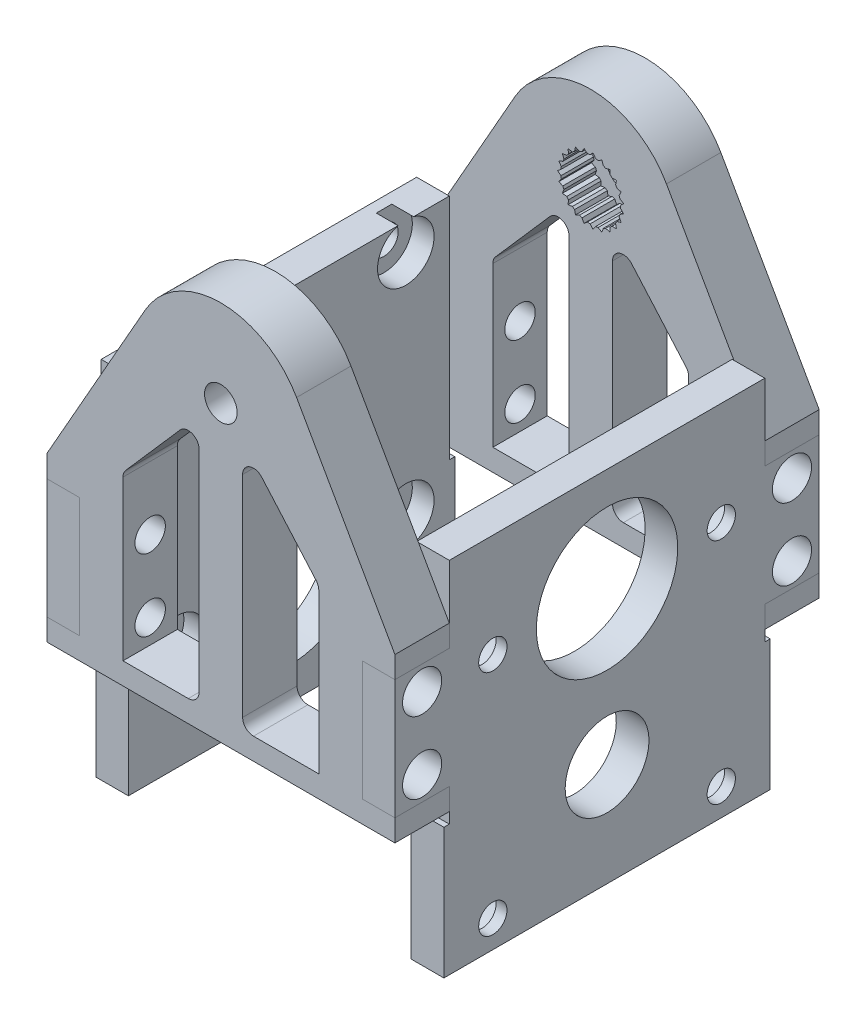
SolidWorks part; units mm, degrees
ref_plane "正面" through (0, 0, 0) normal (0, 0, 1) x (1, 0, 0)
ref_plane "平面" through (0, 0, 0) normal (0, 1, 0) x (1, 0, 0)
ref_plane "右側面" through (0, 0, 0) normal (1, 0, 0) x (0, 0, -1)
sketch "ｽｹｯﾁ1" plane through (0, 0, 0) normal (0, 0, 1) x (1, 0, 0)
  line L0 (-16, -12) -> (-16, -27)
  line L1 (-16, -27) -> (16, -27)
  line L2 (16, -27) -> (16, -12)
  line L3 (16, -12) -> (6.9593, 3.9457)
  line L4 (-6.9593, 3.9457) -> (-16, -12)
  line L5 (0, 0) -> (0, -27) construction
  line L6 (-16, -12) -> (16, -12) construction
  circle A0 centre (0, 0) radius 2.75
  arc A1 (6.9593, 3.9457) -> (-6.9593, 3.9457) centre (0, 0) ccw
  dimension "D1" = 5.5
  dimension "D6" = 8
  dimension "D2" = 16
  dimension "D3" = 16
  dimension "D4" = 12
  dimension "D5" = 15
extrude "ﾎﾞｽ - 押し出し1" add sketch "ｽｹｯﾁ1" along normal blind 3
sketch "ｽｹｯﾁ19" plane through (0, 0, 3) normal (0, 0, 1) x (1, 0, 0)
  line L0 (0, 0) -> (0, 2.75) construction
  line L1 (0, 0) -> (0.3745, 2.7244) construction
  line L2 (0, 0) -> (0.7419, 2.648) construction
  line L3 (0, 0) -> (1.0956, 2.5223) construction
  line L4 (0, 0) -> (1.4289, 2.3497) construction
  line L5 (0, 0) -> (1.7355, 2.1332) construction
  line L6 (0, 0) -> (2.0098, 1.877) construction
  line L7 (0, 0) -> (2.2467, 1.5859) construction
  line L8 (0, 0) -> (2.4417, 1.2652) construction
  line L9 (0, 0) -> (2.5912, 0.9209) construction
  line L10 (0, 0) -> (2.6925, 0.5595) construction
  line L11 (0, 0) -> (2.7436, 0.1877) construction
  line L12 (0, 0) -> (2.7436, -0.1877) construction
  line L13 (0, 0) -> (2.6925, -0.5595) construction
  line L14 (0, 0) -> (2.5912, -0.9209) construction
  line L15 (0, 0) -> (2.4417, -1.2652) construction
  line L16 (0, 0) -> (2.2467, -1.5859) construction
  line L17 (0, 0) -> (2.0098, -1.877) construction
  line L18 (0, 0) -> (1.7355, -2.1332) construction
  line L19 (0, 0) -> (1.4289, -2.3497) construction
  line L20 (0, 0) -> (1.0956, -2.5223) construction
  line L21 (0, 0) -> (0.7419, -2.648) construction
  line L22 (0, 0) -> (0.3745, -2.7244) construction
  line L23 (0, 0) -> (0, -2.75) construction
  line L24 (0, 0) -> (-0.3745, -2.7244) construction
  line L25 (0, 0) -> (-0.7419, -2.648) construction
  line L26 (0, 0) -> (-1.0956, -2.5223) construction
  line L27 (0, 0) -> (-1.4289, -2.3497) construction
  line L28 (0, 0) -> (-1.7355, -2.1332) construction
  line L29 (0, 0) -> (-2.0098, -1.877) construction
  line L30 (0, 0) -> (-2.2467, -1.5859) construction
  line L31 (0, 0) -> (-2.4417, -1.2652) construction
  line L32 (0, 0) -> (-2.5912, -0.9209) construction
  line L33 (0, 0) -> (-2.6925, -0.5595) construction
  line L34 (0, 0) -> (-2.7436, -0.1877) construction
  line L35 (0, 0) -> (-2.7436, 0.1877) construction
  line L36 (0, 0) -> (-2.6925, 0.5595) construction
  line L37 (0, 0) -> (-2.5912, 0.9209) construction
  line L38 (0, 0) -> (-2.4417, 1.2652) construction
  line L39 (0, 0) -> (-2.2467, 1.5859) construction
  line L40 (0, 0) -> (-2.0098, 1.877) construction
  line L41 (0, 0) -> (-1.7355, 2.1332) construction
  line L42 (0, 0) -> (-1.4289, 2.3497) construction
  line L43 (0, 0) -> (-1.0956, 2.5223) construction
  line L44 (0, 0) -> (-0.7419, 2.648) construction
  line L45 (0, 0) -> (-0.3745, 2.7244) construction
  line L46 (0, 0) -> (0.2081, 3.0429) construction
  line L47 (0.2081, 3.0429) -> (-0.0626, 2.7493)
  line L48 (0.2081, 3.0429) -> (0.4364, 2.7152)
  line L49 (-0.0626, 2.7493) -> (0, 0) construction
  line L50 (0, 0) -> (0.4364, 2.7152) construction
  line L51 (1.0214, 2.8739) -> (0.6815, 2.6642)
  line L52 (1.0214, 2.8739) -> (1.1527, 2.4967)
  line L53 (1.7589, 2.4918) -> (1.375, 2.3816)
  line L54 (1.7589, 2.4918) -> (1.7836, 2.0931)
  line L55 (2.3659, 1.9248) -> (1.9666, 1.9223)
  line L56 (2.3659, 1.9248) -> (2.2822, 1.5343)
  line L57 (2.7975, 1.2151) -> (2.4123, 1.3204)
  line L58 (2.7975, 1.2151) -> (2.6115, 0.8617)
  line L59 (3.0216, 0.4153) -> (2.679, 0.6206)
  line L60 (3.0216, 0.4153) -> (2.7472, 0.1252)
  line L61 (3.0216, -0.4153) -> (2.7472, -0.1252)
  line L62 (3.0216, -0.4153) -> (2.679, -0.6206)
  line L63 (2.7975, -1.2151) -> (2.6115, -0.8617)
  line L64 (2.7975, -1.2151) -> (2.4123, -1.3204)
  line L65 (2.3659, -1.9248) -> (2.2822, -1.5343)
  line L66 (2.3659, -1.9248) -> (1.9666, -1.9223)
  line L67 (1.7589, -2.4918) -> (1.7836, -2.0931)
  line L68 (1.7589, -2.4918) -> (1.375, -2.3816)
  line L69 (1.0214, -2.8739) -> (1.1527, -2.4967)
  line L70 (1.0214, -2.8739) -> (0.6815, -2.6642)
  line L71 (0.2081, -3.0429) -> (0.4364, -2.7152)
  line L72 (0.2081, -3.0429) -> (-0.0626, -2.7493)
  line L73 (-0.6205, -2.9862) -> (-0.3123, -2.7322)
  line L74 (-0.6205, -2.9862) -> (-0.802, -2.6304)
  line L75 (-1.4032, -2.708) -> (-1.0379, -2.5466)
  line L76 (-1.4032, -2.708) -> (-1.482, -2.3165)
  line L77 (-2.0818, -2.229) -> (-1.6865, -2.1722)
  line L78 (-2.0818, -2.229) -> (-2.052, -1.8308)
  line L79 (-2.606, -1.5847) -> (-2.21, -1.6366)
  line L80 (-2.606, -1.5847) -> (-2.4699, -1.2093)
  line L81 (-2.9369, -0.8229) -> (-2.5696, -0.9797)
  line L82 (-2.9369, -0.8229) -> (-2.7045, -0.4981)
  line L83 (-3.05, 0) -> (-2.7386, -0.2501)
  line L84 (-3.05, 0) -> (-2.7386, 0.2501)
  line L85 (-2.9369, 0.8229) -> (-2.7045, 0.4981)
  line L86 (-2.9369, 0.8229) -> (-2.5696, 0.9797)
  line L87 (-2.606, 1.5847) -> (-2.4699, 1.2093)
  line L88 (-2.606, 1.5847) -> (-2.21, 1.6366)
  line L89 (-2.0818, 2.229) -> (-2.052, 1.8308)
  line L90 (-2.0818, 2.229) -> (-1.6865, 2.1722)
  line L91 (-1.4032, 2.708) -> (-1.482, 2.3165)
  line L92 (-1.4032, 2.708) -> (-1.0379, 2.5466)
  line L93 (-0.6205, 2.9862) -> (-0.802, 2.6304)
  line L94 (-0.6205, 2.9862) -> (-0.3123, 2.7322)
  circle A0 centre (0, 0) radius 2.75 construction
  arc A1 (0, 2.75) -> (0.3745, 2.7244) centre (0, 0) cw construction
  circle A2 centre (0, 0) radius 3.05 construction
  arc A3 (-0.0626, 2.7493) -> (0.4364, 2.7152) centre (0, 0) cw
  arc A4 (0.6815, 2.6642) -> (1.1527, 2.4967) centre (0, 0) cw
  arc A5 (1.375, 2.3816) -> (1.7836, 2.0931) centre (0, 0) cw
  arc A6 (1.9666, 1.9223) -> (2.2822, 1.5343) centre (0, 0) cw
  arc A7 (2.4123, 1.3204) -> (2.6115, 0.8617) centre (0, 0) cw
  arc A8 (2.679, 0.6206) -> (2.7472, 0.1252) centre (0, 0) cw
  arc A9 (2.7472, -0.1252) -> (2.679, -0.6206) centre (0, 0) cw
  arc A10 (2.6115, -0.8617) -> (2.4123, -1.3204) centre (0, 0) cw
  arc A11 (2.2822, -1.5343) -> (1.9666, -1.9223) centre (0, 0) cw
  arc A12 (1.7836, -2.0931) -> (1.375, -2.3816) centre (0, 0) cw
  arc A13 (1.1527, -2.4967) -> (0.6815, -2.6642) centre (0, 0) cw
  arc A14 (0.4364, -2.7152) -> (-0.0626, -2.7493) centre (0, 0) cw
  arc A15 (-0.3123, -2.7322) -> (-0.802, -2.6304) centre (0, 0) cw
  arc A16 (-1.0379, -2.5466) -> (-1.482, -2.3165) centre (0, 0) cw
  arc A17 (-1.6865, -2.1722) -> (-2.052, -1.8308) centre (0, 0) cw
  arc A18 (-2.21, -1.6366) -> (-2.4699, -1.2093) centre (0, 0) cw
  arc A19 (-2.5696, -0.9797) -> (-2.7045, -0.4981) centre (0, 0) cw
  arc A20 (-2.7386, -0.2501) -> (-2.7386, 0.2501) centre (0, 0) cw
  arc A21 (-2.7045, 0.4981) -> (-2.5696, 0.9797) centre (0, 0) cw
  arc A22 (-2.4699, 1.2093) -> (-2.21, 1.6366) centre (0, 0) cw
  arc A23 (-2.052, 1.8308) -> (-1.6865, 2.1722) centre (0, 0) cw
  arc A24 (-1.482, 2.3165) -> (-1.0379, 2.5466) centre (0, 0) cw
  arc A25 (-0.802, 2.6304) -> (-0.3123, 2.7322) centre (0, 0) cw
  point P7 (0.1877, 2.7436)
  point P52 (0, 0)
  point P60 (0.1877, 2.7436)
  point P126 (0, 0)
  dimension "D2" = 6.1
  dimension "D3" = 10.435
  dimension "D1" = 46
  dimension "D4" = 23
extrude "ｶｯﾄ - 押し出し6" cut sketch "ｽｹｯﾁ19" against normal through all
sketch "ｽｹｯﾁ2" plane through (0, 0, 0) normal (0, 0, -1) x (-1, 0, 0)
  line L5 (16, -12) -> (6.9593, 3.9457)
  line L6 (-6.9593, 3.9457) -> (-16, -12)
  line L7 (-16, -12) -> (-16, -27)
  line L8 (-16, -27) -> (16, -27)
  line L9 (16, -27) -> (16, -12)
  line L10 (16, -12) -> (6.9593, 3.9457)
  line L11 (-6.9593, 3.9457) -> (-16, -12)
  line L12 (-16, -12) -> (-16, -27)
  line L13 (-16, -27) -> (16, -27)
  line L14 (16, -27) -> (16, -12)
  arc A1 (6.9593, 3.9457) -> (-6.9593, 3.9457) centre (0, 0) ccw
  arc A2 (6.9593, 3.9457) -> (-6.9593, 3.9457) centre (0, 0) ccw
  dimension "D1" = 0
extrude "ﾎﾞｽ - 押し出し2" add sketch "ｽｹｯﾁ2" along normal blind 2
ref_plane "平面1" through (0, 0, 33.5) normal (0, 0, 1) x (1, 0, 0)
sketch "ｽｹｯﾁ3" plane through (0, 0, 33.5) normal (0, 0, 1) x (1, 0, 0)
  line L5 (-6.9593, 3.9457) -> (-16, -12)
  line L6 (-16, -12) -> (-16, -27)
  line L7 (-16, -27) -> (16, -27)
  line L8 (16, -27) -> (16, -12)
  line L9 (16, -12) -> (6.9593, 3.9457)
  line L10 (-6.9593, 3.9457) -> (-16, -12)
  line L11 (-16, -12) -> (-16, -27)
  line L12 (-16, -27) -> (16, -27)
  line L13 (16, -27) -> (16, -12)
  line L14 (16, -12) -> (6.9593, 3.9457)
  circle A0 centre (0, 0) radius 2.75 construction
  arc A1 (6.9593, 3.9457) -> (-6.9593, 3.9457) centre (0, 0) ccw
  arc A2 (6.9593, 3.9457) -> (-6.9593, 3.9457) centre (0, 0) ccw
  circle A3 centre (0, 0) radius 2.75 construction
  circle A4 centre (0, 0) radius 3.6
  dimension "D2" = 7.2
  dimension "D1" = 0
extrude "ﾎﾞｽ - 押し出し3" add sketch "ｽｹｯﾁ3" against normal blind 1.5 separate body
sketch "ｽｹｯﾁ4" plane through (0, 0, 33.5) normal (0, 0, 1) x (1, 0, 0)
  line L5 (-6.9593, 3.9457) -> (-16, -12)
  line L6 (-16, -12) -> (-16, -27)
  line L7 (-16, -27) -> (16, -27)
  line L8 (16, -27) -> (16, -12)
  line L9 (16, -12) -> (6.9593, 3.9457)
  line L10 (-6.9593, 3.9457) -> (-16, -12)
  line L11 (-16, -12) -> (-16, -27)
  line L12 (-16, -27) -> (16, -27)
  line L13 (16, -27) -> (16, -12)
  line L14 (16, -12) -> (6.9593, 3.9457)
  arc A1 (6.9593, 3.9457) -> (-6.9593, 3.9457) centre (0, 0) ccw
  arc A2 (6.9593, 3.9457) -> (-6.9593, 3.9457) centre (0, 0) ccw
  dimension "D1" = 0
extrude "ﾎﾞｽ - 押し出し4" add sketch "ｽｹｯﾁ4" along normal blind 3.5
sketch "ｽｹｯﾁ5" plane through (0, 0, -2) normal (0, 0, -1) x (-1, 0, 0)
  line L0 (-16, -12) -> (-16, -27) construction
  line L1 (-16, -14) -> (-13, -14)
  line L2 (-16, -14) -> (-16, -25)
  line L3 (-16, -25) -> (-13, -25)
  line L4 (-13, -14) -> (-13, -25)
  line L5 (-16, -14) -> (-13, -25) construction
  line L6 (-16, -25) -> (-13, -14) construction
  line L7 (16, -27) -> (16, -12) construction
  line L8 (16, -14) -> (13, -14)
  line L9 (16, -14) -> (16, -25)
  line L10 (16, -25) -> (13, -25)
  line L11 (13, -14) -> (13, -25)
  line L12 (16, -14) -> (13, -25) construction
  line L13 (16, -25) -> (13, -14) construction
  line L14 (-16, -27) -> (16, -27) construction
  line L15 (-16, -12) -> (16, -12) construction
  line L16 (-6.9593, 3.9457) -> (-16, -12) construction
  point P4 (-14.5, -19.5)
  point P11 (14.5, -19.5)
  dimension "D1" = 3
  dimension "D2" = 3
  dimension "D3" = 2
  dimension "D4" = 2
extrude "ｶｯﾄ - 押し出し1" cut sketch "ｽｹｯﾁ5" against normal through all
sketch "ｽｹｯﾁ6" plane through (13, 0, 0) normal (1, 0, 0) x (0, 0, -1)
  line L0 (2, -14) -> (-3, -14)
  line L1 (-3, -14) -> (-3, -7)
  line L2 (-3, -7) -> (-32, -7)
  line L3 (-32, -12) -> (-32, 3.9457) construction
  line L4 (-32, -7) -> (-32, -14)
  line L5 (-32, -14) -> (-37, -14)
  line L6 (-37, -14) -> (-37, -25)
  line L7 (-37, -25) -> (-32, -25)
  line L8 (-32, -25) -> (-32, -40)
  line L9 (-32, -40) -> (-3, -40)
  line L10 (-3, -40) -> (-3, -25)
  line L11 (-3, -25) -> (2, -25)
  line L12 (2, -25) -> (2, -14)
  line L13 (-17.5, -7) -> (-17.5, -40) construction
  line L14 (0, 0) -> (-33.5, 0) construction
  line L15 (-7, -37.5) -> (-28, -37.5) construction
  line L16 (-7, -37.5) -> (-7, -16.5) construction
  line L17 (-7, -16.5) -> (-28, -16.5) construction
  line L18 (-28, -37.5) -> (-28, -16.5) construction
  line L19 (-7, -37.5) -> (-28, -16.5) construction
  line L20 (-7, -16.5) -> (-28, -37.5) construction
  line L21 (-33.5, 3.3394) -> (-33.5, -3.3394) construction
  line L22 (2, -23.5) -> (-37, -23.5) construction
  circle A0 centre (-17.5, -16.5) radius 6.5
  circle A1 centre (-28, -16.5) radius 1.3
  circle A2 centre (-7, -16.5) radius 1.3
  circle A3 centre (-28, -37.5) radius 1.3
  circle A4 centre (-7, -37.5) radius 1.3
  circle A5 centre (-17.5, -30.5) radius 6.5 construction
  circle A6 centre (-17.5, -30.5) radius 3.85
  point P24 (-17.5, -27)
  point P43 (-17.5, -23.5)
  dimension "D6" = 2.6
  dimension "D8" = 13
  dimension "D10" = 7.7
  dimension "D1" = 21
  dimension "D2" = 21
  dimension "D3" = 14.5
  dimension "D4" = 13
  dimension "D5" = 21
  dimension "D7" = 20
  dimension "D9" = 27
extrude "ﾎﾞｽ - 押し出し5" add sketch "ｽｹｯﾁ6" along normal up to surface (3 mm away) separate body up to face at (16, -13, 0.5)
sketch "ｽｹｯﾁ8" plane through (-13, 0, 0) normal (-1, 0, 0) x (0, 0, 1)
  line L0 (3, -7) -> (3, -40) construction
  line L1 (32, -7) -> (32, -40) construction
  line L2 (3, -23.5) -> (32, -23.5) construction
  line L12 (-2, -14) -> (-2, -25)
  line L13 (-2, -25) -> (3, -25)
  line L14 (3, -25) -> (3, -40)
  line L15 (3, -40) -> (32, -40)
  line L16 (32, -40) -> (32, -25)
  line L17 (32, -25) -> (37, -25)
  line L18 (37, -25) -> (37, -14)
  line L19 (37, -14) -> (32, -14)
  line L20 (32, -14) -> (32, -7)
  line L21 (32, -7) -> (3, -7)
  line L22 (3, -7) -> (3, -14)
  line L23 (3, -14) -> (-2, -14)
  line L24 (-2, -14) -> (-2, -25)
  line L25 (-2, -25) -> (3, -25)
  line L26 (3, -25) -> (3, -40)
  line L27 (3, -40) -> (32, -40)
  line L28 (32, -40) -> (32, -25)
  line L29 (32, -25) -> (37, -25)
  line L30 (37, -25) -> (37, -14)
  line L31 (37, -14) -> (32, -14)
  line L32 (32, -14) -> (32, -7)
  line L33 (32, -7) -> (3, -7)
  line L34 (3, -7) -> (3, -14)
  line L35 (3, -14) -> (-2, -14)
  circle A0 centre (28, -37.5) radius 1.3 construction
  circle A1 centre (28, -16.5) radius 1.3 construction
  circle A2 centre (7, -37.5) radius 1.3 construction
  circle A3 centre (17.5, -16.5) radius 6.5 construction
  circle A4 centre (7, -16.5) radius 1.3 construction
  circle A5 centre (28, -37.5) radius 1.3 construction
  circle A6 centre (28, -16.5) radius 1.3 construction
  circle A7 centre (7, -37.5) radius 1.3 construction
  circle A8 centre (17.5, -16.5) radius 6.5 construction
  circle A9 centre (7, -16.5) radius 1.3 construction
  circle A10 centre (28, -9.5) radius 1.3
  circle A11 centre (7, -9.5) radius 1.3
  circle A12 centre (28, -30.5) radius 1.3
  circle A13 centre (17.5, -30.5) radius 6.5
  circle A14 centre (7, -30.5) radius 1.3
  circle A15 centre (17.5, -16.5) radius 3.85
  dimension "D2" = 7.7
  dimension "D1" = 0
extrude "ﾎﾞｽ - 押し出し6" add sketch "ｽｹｯﾁ8" along normal up to surface (3 mm away) separate body up to face at (-16, -26, 0.5)
sketch "ｽｹｯﾁ7" plane through (0, 0, -2) normal (0, 0, -1) x (-1, 0, 0)
  line L0 (0, 0) -> (0, -13.5) construction
  line L1 (-16, -27) -> (16, -27) construction
  line L2 (9, -25) -> (-9, -25) construction
  line L3 (9, -25) -> (9, -2) construction
  line L4 (9, -2) -> (-9, -2) construction
  line L5 (-9, -25) -> (-9, -2) construction
  line L6 (9, -25) -> (-9, -2) construction
  line L7 (9, -2) -> (-9, -25) construction
  line L8 (-13, -25) -> (-13, -14) construction
  line L9 (-9, -25) -> (-3, -25)
  line L10 (-2, -24) -> (-2, -4.6614)
  line L11 (-3.7526, -4.0029) -> (-8.7526, -9.7172)
  line L12 (-9, -10.3757) -> (-9, -25)
  line L15 (-16, -14) -> (-13, -14) construction
  line L16 (9, -25) -> (3, -25)
  line L17 (9, -10.3757) -> (9, -25)
  line L18 (3.7526, -4.0029) -> (8.7526, -9.7172)
  line L19 (2, -24) -> (2, -4.6614)
  circle A0 centre (0, 0) radius 1.5
  arc A2 (3, -25) -> (2, -24) centre (3, -24) cw
  arc A3 (-3, -25) -> (-2, -24) centre (-3, -24) ccw
  arc A5 (-2, -4.6614) -> (-3.7526, -4.0029) centre (-3, -4.6614) ccw
  arc A6 (3.7526, -4.0029) -> (2, -4.6614) centre (3, -4.6614) ccw
  arc A7 (9, -10.3757) -> (8.7526, -9.7172) centre (8, -10.3757) ccw
  arc A8 (-8.7526, -9.7172) -> (-9, -10.3757) centre (-8, -10.3757) ccw
  point P28 (2, -25)
  point P31 (-2, -25)
  point P37 (-2, -2)
  point P40 (2, -2)
  point P43 (9, -10)
  point P46 (-9, -10)
  dimension "D1" = 3
  dimension "D8" = 1
  dimension "D2" = 2
  dimension "D3" = 4
  dimension "D4" = 23
  dimension "D5" = 4
  dimension "D6" = 7
extrude "ｶｯﾄ - 押し出し2" cut sketch "ｽｹｯﾁ7" against normal through all
sketch "ｽｹｯﾁ10" plane through (16, 0, 0) normal (1, 0, 0) x (0, 0, -1)
  line L4 (-34.5, -12) -> (-34.5, -27) construction
  line L5 (-32, -12) -> (-37, -12) construction
  line L6 (-32, -27) -> (-37, -27) construction
  line L8 (-0.5, -12) -> (-0.5, -27) construction
  line L9 (-3, -12) -> (2, -12) construction
  line L10 (-3, -27) -> (2, -27) construction
  line L11 (-37, -14) -> (-32, -14) construction
  line L14 (-32, -25) -> (-37, -25) construction
  line L15 (-3, -14) -> (2, -14) construction
  line L16 (2, -25) -> (-3, -25) construction
  point P26 (-34.5, -16.2)
  point P28 (-34.5, -22.8)
  point P30 (-0.5, -16.2)
  point P32 (-0.5, -22.8)
  dimension "D1" = 2.2
  dimension "D2" = 2.2
  dimension "D3" = 2.2
  dimension "D4" = 2.2
hole_wizard "Ø2.8 (2.8) 直径の穴1" positions "ｽｹｯﾁ10" profile "ｽｹｯﾁ11" hole size "Ø2.8" standard "JIS"
sketch "ｽｹｯﾁ11" plane through (16, -22.8, 0.5) normal (0, 1, 0) x (0, 0, -1)
  line L0 (0, 0) -> (0, 14)
  line L1 (0, 14) -> (1.4, 13.1588)
  line L2 (1.4, 13.1588) -> (1.4, 0)
  line L5 (1.4, 0) -> (0, 0)
  line L10 (0, 14) -> (-1.4, 13.1588) construction
  line L11 (0, -6.35) -> (0, 107.95) construction
  dimension "穴の直径" = 2.8
  dimension "穴の深さ" = 14
  dimension "ﾄﾞﾘﾙ角度" = 118
hole_wizard "Ø2.8 (2.8) 直径の穴2" positions "ｽｹｯﾁ12" profile "ｽｹｯﾁ13" hole size "Ø2.8" standard "JIS"
sketch "ｽｹｯﾁ12" plane through (-16, 0, 0) normal (-1, 0, 0) x (0, 0, 1)
  point P0 (34.5, -16.2)
  point P3 (34.5, -22.8)
  point P6 (0.5, -16.2)
  point P9 (0.5, -22.8)
sketch "ｽｹｯﾁ13" plane through (-16, -16.2, 34.5) normal (0, 1, 0) x (0, 0, 1)
  line L0 (0, 0) -> (0, 14)
  line L1 (0, 14) -> (1.4, 13.1588)
  line L2 (1.4, 13.1588) -> (1.4, 0)
  line L5 (1.4, 0) -> (0, 0)
  line L10 (0, 14) -> (-1.4, 13.1588) construction
  line L11 (0, -6.35) -> (0, 107.95) construction
  dimension "穴の直径" = 2.8
  dimension "穴の深さ" = 14
  dimension "ﾄﾞﾘﾙ角度" = 118
hole_wizard "Ø3.6 (3.6) 直径の穴1" positions "ｽｹｯﾁ14" profile "ｽｹｯﾁ16" hole size "Ø3.6" standard "JIS" end condition through all
sketch "ｽｹｯﾁ14" plane through (16, 0, 0) normal (1, 0, 0) x (0, 0, -1)
  point P0 (-34.5, -16.2)
  point P3 (-34.5, -22.8)
  point P6 (-0.5, -16.2)
  point P9 (-0.5, -22.8)
sketch "ｽｹｯﾁ16" plane through (16, -16.2, 34.5) normal (0, 1, 0) x (0, 0, -1)
  line L0 (0, 0) -> (0, 32)
  line L1 (0, 32) -> (1.8, 32)
  line L2 (1.8, 32) -> (1.8, 0)
  line L5 (1.8, 0) -> (0, 0)
  line L11 (0, -6.35) -> (0, 107.95) construction
  dimension "通し穴の直径" = 3.6
  dimension "通し穴の深さ" = 32
sketch "ｽｹｯﾁ17" plane through (13, 0, 0) normal (-1, 0, 0) x (0, 0, 1)
  circle A0 centre (28, -37.5) radius 1.3 construction
  circle A1 centre (7, -37.5) radius 1.3 construction
  circle A2 centre (28, -16.5) radius 1.3 construction
  circle A3 centre (7, -16.5) radius 1.3 construction
  circle A4 centre (28, -37.5) radius 1.3 construction
  circle A5 centre (7, -37.5) radius 1.3 construction
  circle A6 centre (28, -16.5) radius 1.3 construction
  circle A7 centre (7, -16.5) radius 1.3 construction
  circle A8 centre (7, -16.5) radius 2.6
  circle A9 centre (7, -37.5) radius 2.6
  circle A10 centre (28, -37.5) radius 2.6
  circle A11 centre (28, -16.5) radius 2.6
  dimension "D1" = 5.2
extrude "ｶｯﾄ - 押し出し4" cut sketch "ｽｹｯﾁ17" against normal blind 2
sketch "ｽｹｯﾁ18" plane through (-13, 0, 0) normal (1, 0, 0) x (0, 0, -1)
  circle A0 centre (-28, -30.5) radius 1.3 construction
  circle A1 centre (-28, -9.5) radius 1.3 construction
  circle A2 centre (-7, -9.5) radius 1.3 construction
  circle A3 centre (-28, -30.5) radius 1.3 construction
  circle A4 centre (-28, -9.5) radius 1.3 construction
  circle A5 centre (-7, -9.5) radius 1.3 construction
  circle A6 centre (-7, -30.5) radius 1.3 construction
  circle A7 centre (-7, -30.5) radius 1.3 construction
  circle A8 centre (-28, -9.5) radius 2.6
  circle A9 centre (-28, -30.5) radius 2.6
  circle A10 centre (-7, -30.5) radius 2.6
  circle A11 centre (-7, -9.5) radius 2.6
  dimension "D1" = 5.2
extrude "ｶｯﾄ - 押し出し5" cut sketch "ｽｹｯﾁ18" against normal blind 2
sketch "ｽｹｯﾁ20" plane through (0, 0, 32) normal (0, 0, 1) x (1, 0, 0)
  line L0 (-13, -40) -> (-13, -25) construction
  line L1 (-16, -40) -> (-13, -40)
  line L2 (-16, -40) -> (-16, -28)
  line L3 (-16, -28) -> (-13, -28)
  line L4 (-13, -40) -> (-13, -28)
  line L5 (16, -40) -> (16, -25) construction
  line L6 (13, -40) -> (16, -40)
  line L7 (13, -40) -> (13, -28)
  line L8 (13, -28) -> (16, -28)
  line L9 (16, -40) -> (16, -28)
  line L10 (-16, -27) -> (16, -27) construction
  dimension "D1" = 1
extrude "ﾎﾞｽ - 押し出し7" add sketch "ｽｹｯﾁ20" along normal blind 0.5
sketch "ｽｹｯﾁ21" plane through (0, 0, 3) normal (0, 0, -1) x (-1, 0, 0)
  line L4 (-16, -40) -> (-13, -40)
  line L5 (-16, -28) -> (-16, -40)
  line L6 (-13, -28) -> (-16, -28)
  line L7 (-13, -40) -> (-13, -28)
  line L8 (-16, -40) -> (-13, -40)
  line L9 (-16, -28) -> (-16, -40)
  line L10 (-13, -28) -> (-16, -28)
  line L11 (-13, -40) -> (-13, -28)
  line L12 (13, -40) -> (16, -40)
  line L13 (13, -28) -> (13, -40)
  line L14 (16, -28) -> (13, -28)
  line L15 (16, -40) -> (16, -28)
  line L16 (13, -40) -> (16, -40)
  line L17 (13, -28) -> (13, -40)
  line L18 (16, -28) -> (13, -28)
  line L19 (16, -40) -> (16, -28)
  dimension "D1" = 0
  dimension "D2" = 0
extrude "ﾎﾞｽ - 押し出し8" add sketch "ｽｹｯﾁ21" along normal blind 0.5
sketch "ｽｹｯﾁ22" plane through (-13, 0, 0) normal (1, 0, 0) x (0, 0, -1)
  circle A0 centre (-17.5, -16.5) radius 4.2
  dimension "D1" = 8.4
extrude "ｶｯﾄ - 押し出し7" cut sketch "ｽｹｯﾁ22" against normal through all
equation "\"D2@ｽｹｯﾁ5\"=\"D1@ｽｹｯﾁ5\""
equation "\"D8@ｽｹｯﾁ6\"=12.5+0.5"
equation "\"D1@ｽｹｯﾁ10\"=\"D2@ｽｹｯﾁ10\""
equation "\"D3@ｽｹｯﾁ10\"=\"D2@ｽｹｯﾁ10\""
equation "\"D4@ｽｹｯﾁ10\"=\"D2@ｽｹｯﾁ10\""
equation "\"D3@ｽｹｯﾁ19\"=360/23*2/3"
